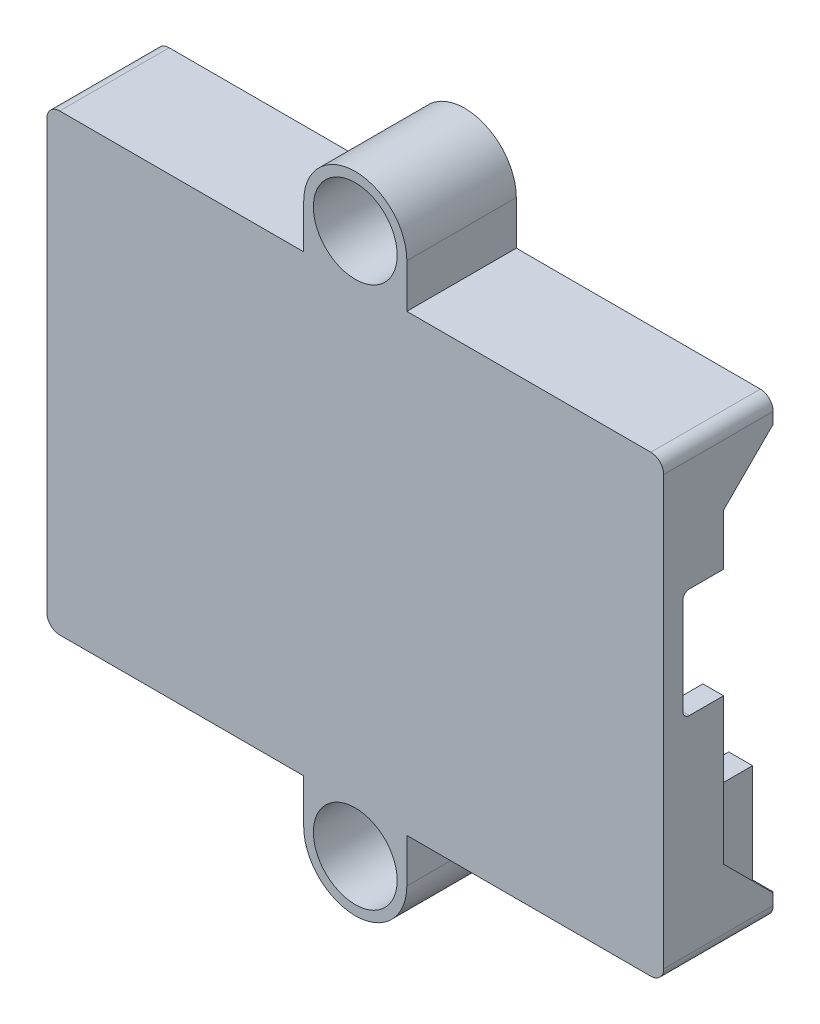
SolidWorks part; units mm, degrees
ref_plane "Front Plane" through (0, 0, 0) normal (0, 0, 1) x (1, 0, 0)
ref_plane "Top Plane" through (0, 0, 0) normal (0, 1, 0) x (1, 0, 0)
ref_plane "Right Plane" through (0, 0, 0) normal (1, 0, 0) x (0, 0, -1)
sketch "Sketch1" plane through (0, 0, 0) normal (0, 0, 1) x (1, 0, 0)
  line L0 (-22.325, 16) -> (22.325, 16)
  line L1 (-23.925, -17.6) -> (23.925, -17.6)
  line L2 (-23.925, -17.6) -> (-23.925, 17.6)
  line L3 (-23.925, 17.6) -> (23.925, 17.6)
  line L4 (23.925, -17.6) -> (23.925, 17.6)
  line L5 (22.325, -16) -> (22.325, 16)
  line L6 (-22.325, -16) -> (22.325, -16)
  line L7 (-22.325, -16) -> (-22.325, 16)
  line L8 (22.925, 17.6) -> (4, 17.6) construction
  line L9 (-23.925, 16.6) -> (-23.925, -16.6) construction
  line L10 (23.925, 15.6) -> (23.925, 16.6) construction
  line L11 (-22.925, -17.6) -> (-4, -17.6) construction
  dimension "D1" = 1.6
extrude "Boss-Extrude1" add sketch "Sketch1" along normal offset from surface (6.99 mm away) 0.5 offset beyond the face yes
sketch "Sketch2" plane through (0, 0, 6.99) normal (0, 0, 1) x (1, 0, 0)
  line L4 (23.925, 17.6) -> (-23.925, 17.6)
  line L5 (-23.925, 17.6) -> (-23.925, -17.6)
  line L6 (-23.925, -17.6) -> (23.925, -17.6)
  line L7 (23.925, -17.6) -> (23.925, 17.6)
  line L8 (23.925, 17.6) -> (-23.925, 17.6)
  line L9 (-23.925, 17.6) -> (-23.925, -17.6)
  line L10 (-23.925, -17.6) -> (23.925, -17.6)
  line L11 (23.925, -17.6) -> (23.925, 17.6)
  dimension "D1" = 0
extrude "Boss-Extrude2" add sketch "Sketch2" along normal blind 1.5
sketch "Sketch3" plane through (23.925, 0, 0) normal (1, 0, 0) x (0, 0, -1)
  line L3 (-0.0707, 15.6707) -> (0, 15.6707)
  line L4 (0, -17.6) -> (0, 17.6) construction
  line L5 (-0.0707, -15.6707) -> (0, -15.6707)
  line L6 (-0.0707, 15.6707) -> (-3.85, 11.8914)
  line L7 (-3.85, 11.8914) -> (-3.85, -11.8914)
  line L8 (-3.85, -11.8914) -> (-0.0707, -15.6707)
  line L9 (-0.0707, 15.6707) -> (-3.85, 11.8914)
  line L10 (-3.85, 11.8914) -> (-3.85, -11.8914)
  line L11 (-3.85, -11.8914) -> (-0.0707, -15.6707)
  line L12 (0, 15.6707) -> (0, -15.6707)
  dimension "D1" = 0.1
extrude "Cut-Extrude1" cut sketch "Sketch3" against normal up to next
sketch "Sketch4" plane through (23.925, 0, 0) normal (1, 0, 0) x (0, 0, -1)
  line L0 (-3.5, 7.9205) -> (-3.5, -0.5795) construction
  line L1 (-3.5, -0.5795) -> (-7, -0.5795) construction
  line L2 (-7, 7.9205) -> (-7, -0.5795) construction
  line L3 (-3.5, 7.9205) -> (-7, 7.9205) construction
  line L4 (-3.5, 7.9205) -> (-3.5, -0.5795)
  line L5 (-3.5, -0.5795) -> (-7, -0.5795)
  line L6 (-7, 7.9205) -> (-7, -0.5795)
  line L7 (-3.5, 7.9205) -> (-7, 7.9205)
extrude "Cut-Extrude2" cut sketch "Sketch4" against normal up to surface (1.6 mm away) up to face at (22.325, 0, 2.1821)
sketch "Sketch6" plane through (0, -17.6, 0) normal (0, -1, 0) x (1, 0, 0)
  line L0 (20.48, -0.28) -> (20.48, 6.32) construction
  line L1 (20.48, -0.28) -> (10.08, -0.28) construction
  line L2 (10.08, -0.28) -> (10.08, 6.32) construction
  line L3 (20.48, 6.32) -> (10.08, 6.32) construction
  line L4 (20.48, -0.28) -> (20.48, 6.32)
  line L5 (20.48, -0.28) -> (10.08, -0.28)
  line L6 (10.08, -0.28) -> (10.08, 6.32)
  line L7 (20.48, 6.32) -> (10.08, 6.32)
extrude "Cut-Extrude3" cut sketch "Sketch6" against normal up to next
fillet "Fillet1" radius 1 4 edges at (-23.925, 17.6, 4.245) (23.925, 17.6, 4.245) (-23.925, -17.6, 4.245) (23.925, -17.6, 4.245)
fillet "Fillet2" radius 0.5 4 edges at (23.125, -0.5795, 7) (20.48, -16.8, 6.32) (23.125, 7.9205, 7) (10.08, -16.8, 6.32)
sketch "Sketch7" plane through (0, 0, 8.49) normal (0, 0, 1) x (1, 0, 0)
  line L0 (4, -17.6) -> (4, -21) construction
  line L1 (-4, -17.6) -> (-4, -21) construction
  line L2 (4, -17.6) -> (4, -21)
  line L3 (-4, -17.6) -> (-4, -21)
  line L4 (-4, -17.6) -> (4, -17.6)
  line L5 (-4, 17.6) -> (-4, 21) construction
  line L6 (4, 17.6) -> (4, 21) construction
  line L7 (-4, 17.6) -> (-4, 21)
  line L8 (4, 17.6) -> (4, 21)
  line L9 (4, 17.6) -> (-4, 17.6)
  circle A0 centre (0, -21) radius 1.75 construction
  arc A1 (-4, -21) -> (4, -21) centre (0, -21) ccw construction
  circle A2 centre (0, -21) radius 1.75
  arc A3 (-4, -21) -> (4, -21) centre (0, -21) ccw
  circle A4 centre (0, 21) radius 1.75 construction
  arc A5 (4, 21) -> (-4, 21) centre (0, 21) ccw construction
  circle A6 centre (0, 21) radius 1.75
  arc A7 (4, 21) -> (-4, 21) centre (0, 21) ccw
extrude "Boss-Extrude3" add sketch "Sketch7" against normal up to surface (8.49 mm away) up to face at (-0.2286, 3.7037, 0)
sketch "Sketch8" plane through (0, 0, 8.49) normal (0, 0, 1) x (1, 0, 0)
  circle A0 centre (0, 21) radius 3.25
  circle A1 centre (0, -21) radius 3.25
  dimension "D1" = 6.5
extrude "Cut-Extrude4" cut sketch "Sketch8" against normal offset from surface (6.49 mm away) 2 up to face at (22.3703, -16.4784, 0)
sketch "Sketch9" plane through (0, 0, 0) normal (0, 0, -1) x (-1, 0, 0)
  line L0 (-4, -17.6) -> (-4, -16) construction
  line L1 (-10.08, -16) -> (-8.48, -16)
  line L2 (-10.08, -16) -> (-10.08, -8)
  line L3 (-10.08, -8) -> (-8.48, -8)
  line L4 (-8.48, -16) -> (-8.48, -8)
  line L5 (22.325, -16) -> (-10.08, -16) construction
  line L6 (-22.325, -0.5795) -> (-22.325, -11.8914) construction
  line L7 (-20.48, -16) -> (-22.325, -16)
  line L8 (-20.48, -16) -> (-20.48, -8)
  line L9 (-20.48, -8) -> (-22.325, -8)
  line L10 (-22.325, -16) -> (-22.325, -8)
  dimension "D1" = 8
extrude "Boss-Extrude4" add sketch "Sketch9" against normal up to surface (6.99 mm away) up to face at (7.4417, 1.2235, 6.99)
